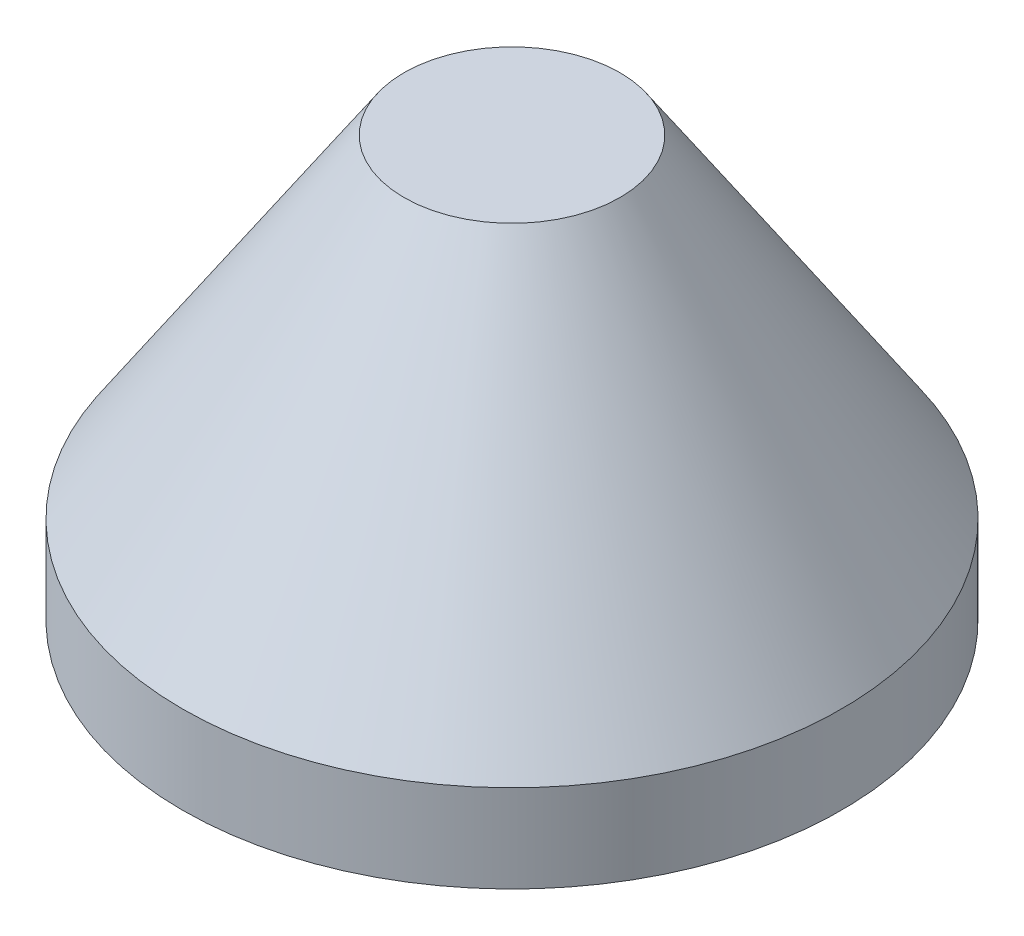
SolidWorks part; units mm, degrees
ref_plane "Front Plane" through (0, 0, 0) normal (0, 0, 1) x (1, 0, 0)
ref_plane "Top Plane" through (0, 0, 0) normal (0, 1, 0) x (1, 0, 0)
ref_plane "Right Plane" through (0, 0, 0) normal (1, 0, 0) x (0, 0, -1)
sketch "Sketch2" plane through (0, 0, 0) normal (1, 0, 0) x (0, 0, -1)
  line L1 (95.4405, 0) -> (95.4405, 25.4)
  line L3 (0, 121.605) -> (31.3042, 121.605)
  line L4 (95.4405, 25.4) -> (31.3042, 121.605)
  line L5 (0, 118.43) -> (28.9676, 118.43)
  line L6 (28.9676, 118.43) -> (92.2655, 23.4825)
  line L7 (92.2655, 23.4825) -> (92.2655, 0)
  line L8 (0, 121.605) -> (0, 118.43)
  line L9 (92.2655, 0) -> (95.4405, 0)
  line L10 (0, 171.8573) -> (0, -25.2724) construction
  dimension "D1" = 92.2655
  dimension "D2" = 25.4
  dimension "D4" = 31.3042
  dimension "D5" = 3.175
  dimension "D6" = 3.175
  dimension "D7" = 180
revolve "Revolve1" add sketch "Sketch2" angle 360 about L10
